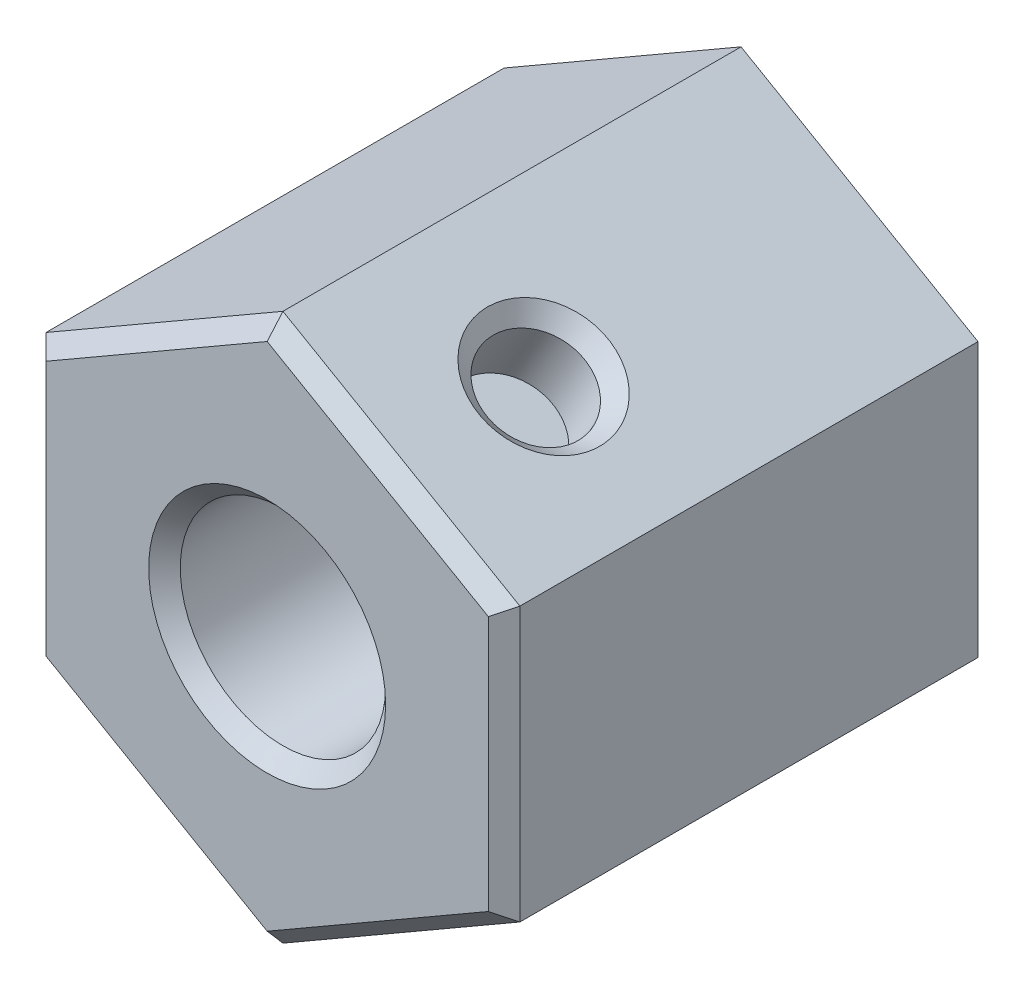
SolidWorks part; units mm, degrees
ref_plane "Front" through (0, 0, 0) normal (0, 0, 1) x (1, 0, 0)
ref_plane "Top" through (0, 0, 0) normal (0, 1, 0) x (1, 0, 0)
ref_plane "Right" through (0, 0, 0) normal (1, 0, 0) x (0, 0, -1)
sketch "Sketch1" plane through (0, 0, 0) normal (0, 0, 1) x (1, 0, 0)
  line L1 (0, 8.6603) -> (-7.5, 4.3301)
  line L2 (-7.5, 4.3301) -> (-7.5, -4.3301)
  line L3 (-7.5, -4.3301) -> (0, -8.6603)
  line L4 (0, -8.6603) -> (7.5, -4.3301)
  line L5 (7.5, -4.3301) -> (7.5, 4.3301)
  line L6 (7.5, 4.3301) -> (0, 8.6603)
  circle A0 centre (0, 0) radius 7.5 construction
  dimension "D1" = 15
extrude "Boss-Extrude1" add sketch "Sketch1" along normal blind 15
sketch "Sketch2" plane through (0, 0, 15) normal (0, 0, 1) x (1, 0, 0)
  circle A0 centre (0, 0) radius 3.25
  dimension "D1" = 6.5
extrude "Cut-Extrude1" cut sketch "Sketch2" against normal blind 15
sketch "Sketch3" plane through (0, 0, 0) normal (0, 0, -1) x (-1, 0, 0)
  line L0 (-7.5, 4.3301) -> (0, 8.6603) construction
  line L1 (0, 6.0044) -> (-5.2, 3.0022)
  line L2 (-5.2, 3.0022) -> (-5.2, -3.0022)
  line L3 (-5.2, -3.0022) -> (0, -6.0044)
  line L4 (0, -6.0044) -> (5.2, -3.0022)
  line L5 (5.2, -3.0022) -> (5.2, 3.0022)
  line L6 (5.2, 3.0022) -> (0, 6.0044)
  circle A0 centre (0, 0) radius 5.2 construction
  dimension "D1" = 10.4
extrude "Cut-Extrude2" cut sketch "Sketch3" against normal blind 2.5
sketch "Sketch4" plane through (3.75, 6.4952, 0) normal (0.5, 0.866, 0) x (0.866, -0.5, 0)
  line L0 (4.3301, 0) -> (-4.3301, 0) construction
  circle A0 centre (0, -10) radius 1.55
  point P5 (0, 0)
  dimension "D1" = 3.1
  dimension "D2" = 10
extrude "Cut-Extrude3" cut sketch "Sketch4" against normal blind 2.5
ref_axis "Axis1" through (0, 0, 2.5) along (0, 0, 1)
pattern_circular "CirPattern1" count 3 over 360 about axis through (0, 0, 15) along (0, 0, 1) of "Cut-Extrude3"
chamfer "Chamfer1" distance 0.5 angle 45 7 edges at (7.5, 0, 15) (3.75, -6.4952, 15) (-3.75, -6.4952, 15) (-7.5, 0, 15) (-3.75, 6.4952, 15) (3.75, 6.4952, 15) (3.25, 0, 15)
chamfer "Chamfer2" distance 0.5 angle 45 3 edges at (-7.5, -1.55, 10) (5.0923, -5.7202, 10) (2.4077, 7.2702, 10)
chamfer "Chamfer3" distance 0.5 angle 45 1 edges at (-3.25, 0, 2.5)
chamfer "Chamfer4" distance 0.4 angle 45 6 edges at (-2.6, 4.5033, 0) (2.6, 4.5033, 0) (5.2, 0, 0) (2.6, -4.5033, 0) (-2.6, -4.5033, 0) (-5.2, 0, 0)
